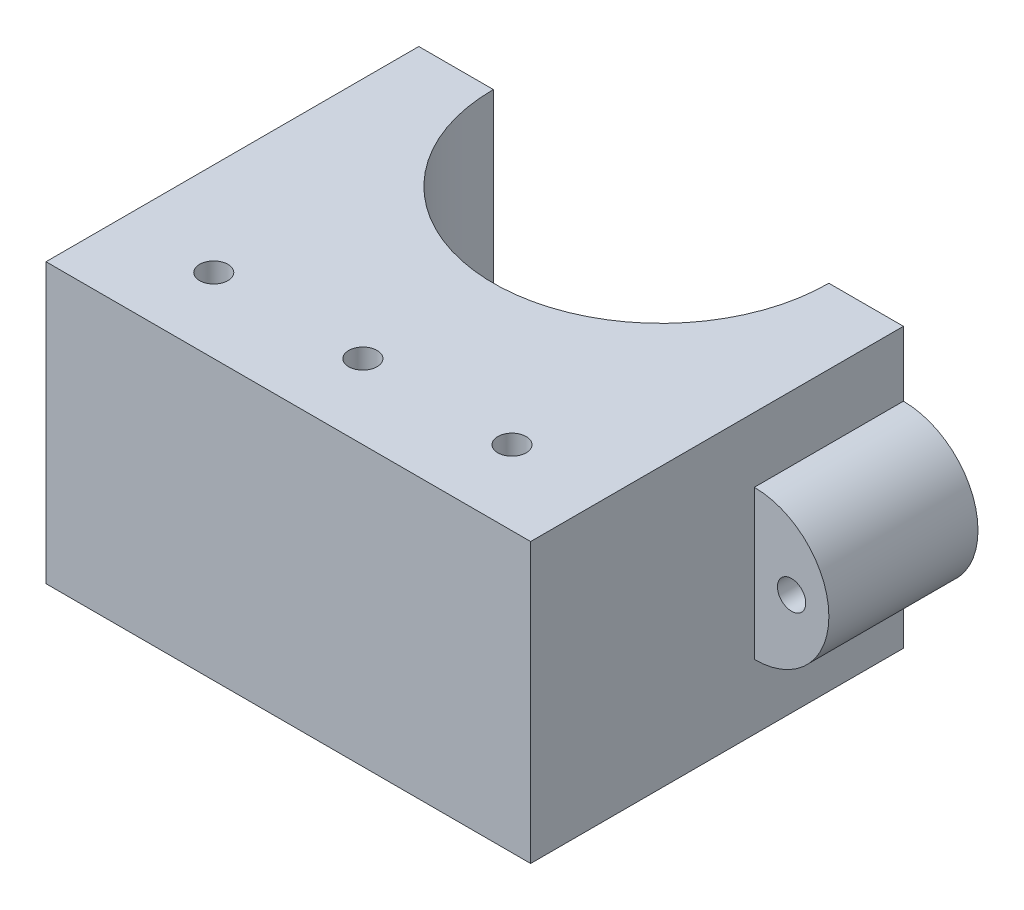
SolidWorks part; units mm, degrees
material "Mahogany"
ref_plane "Front Plane" through (0, 0, 0) normal (0, 0, 1) x (1, 0, 0)
ref_plane "Top Plane" through (0, 0, 0) normal (0, 1, 0) x (1, 0, 0)
ref_plane "Right Plane" through (0, 0, 0) normal (1, 0, 0) x (0, 0, -1)
sketch "Sketch1" plane through (0, 0, 0) normal (0, 1, 0) x (1, 0, 0)
  line L0 (0, 0) -> (0, 63.5)
  line L1 (0, 63.5) -> (12.7, 63.5)
  line L2 (69.85, 63.5) -> (82.55, 63.5)
  line L3 (82.55, 63.5) -> (82.55, 0)
  line L4 (82.55, 0) -> (0, 0)
  arc A0 (12.7, 63.5) -> (69.85, 63.5) centre (41.275, 63.5) ccw
  dimension "D3" = 28.575
  dimension "D1" = 12.7
  dimension "D2" = 12.7
  dimension "D4" = 82.55
  dimension "D5" = 63.5
extrude "Boss-Extrude1" add sketch "Sketch1" along normal blind 47.498 contours A0 L2 L3 L4 L0 L1
sketch "Sketch2" plane through (0, 47.498, 0) normal (0, 1, 0) x (1, 0, 0)
  line L0 (82.55, 0) -> (0, 0) construction
  line L1 (82.55, 63.5) -> (82.55, 0) construction
  line L4 (0, 0) -> (0, 63.5) construction
  circle A0 centre (15.875, 12.7) radius 2.413
  circle A1 centre (41.275, 12.7) radius 2.413
  circle A2 centre (66.675, 12.7) radius 2.413
  dimension "D3" = 4.826
  dimension "D4" = 4.826
  dimension "D5" = 4.826
  dimension "D7" = 12.7
  dimension "D8" = 12.7
  dimension "D10" = 15.875
  dimension "D1" = 25.4
  dimension "D2" = 25.4
  dimension "D6" = 12.7
  dimension "D9" = 15.875
extrude "Cut-Extrude3" cut sketch "Sketch2" along normal through all and the other way through all contours A0
extrude "Cut-Extrude4" cut sketch "Sketch2<4>" against normal through all
sketch "Sketch2<4>" plane through (0, 47.498, 0) normal (0, 1, 0) x (1, 0, 0) same geometry as "Sketch2"
sketch "Sketch6" plane through (0, 0, -63.5) normal (0, 0, -1) x (-1, 0, 0)
  line L0 (0, 47.498) -> (0, 0) construction
  line L1 (-82.55, 47.498) -> (-82.55, 0) construction
  circle A0 centre (0, 24.2906) radius 12.7
  circle A1 centre (-82.55, 23.749) radius 12.7
  dimension "D1" = 25.4
  dimension "D2" = 25.4
extrude "Boss-Extrude5" add sketch "Sketch6" against normal blind 25.4 contours A1
extrude "Boss-Extrude6" add sketch "Sketch6<6>" against normal blind 25.4
sketch "Sketch6<6>" plane through (0, 0, -63.5) normal (0, 0, -1) x (-1, 0, 0) same geometry as "Sketch6"
sketch "Sketch8" plane through (0, 0, -63.5) normal (0, 0, -1) x (-1, 0, 0)
  circle A1 centre (-88.9, 23.749) radius 2.413
  dimension "D1" = 4.826
extrude "Cut-Extrude5" cut sketch "Sketch8" against normal blind 25.4 contours A1
sketch "Sketch9" plane through (0, 0, -63.5) normal (0, 0, -1) x (-1, 0, 0)
  circle A1 centre (-545.1254, 23.7573) radius 106.9223
  circle A2 centre (6.2967, 24.1395) radius 2.413
  dimension "D1" = 4.826
extrude "Cut-Extrude6" cut sketch "Sketch9" against normal blind 25.4 contours A2
equation "\".5625 \"=1.14789"
